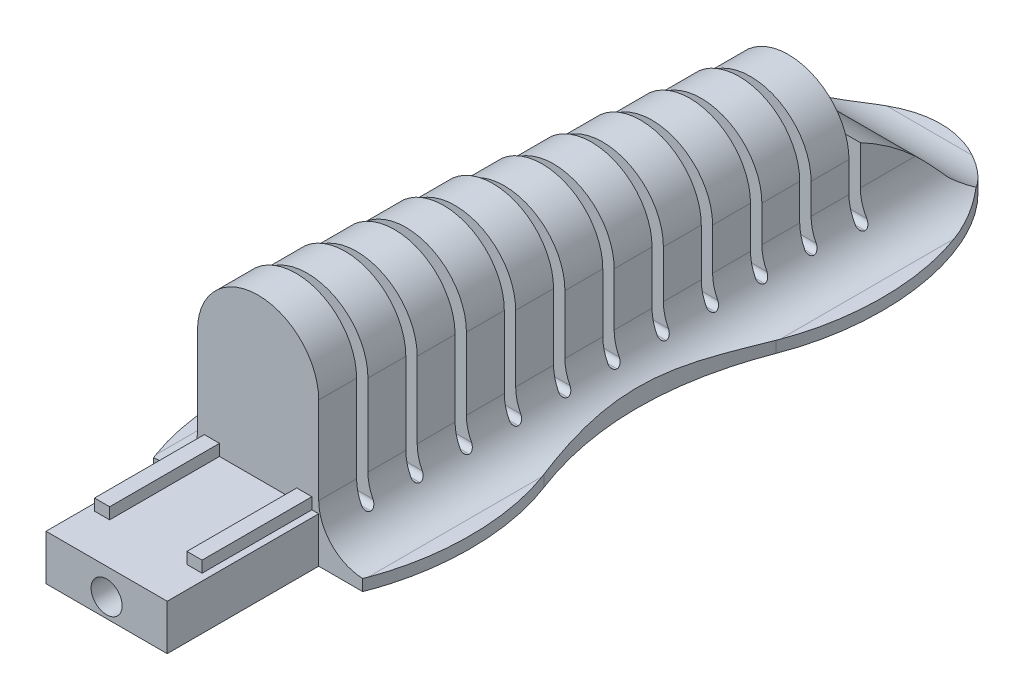
SolidWorks part; units mm, degrees
ref_plane "Front Plane" through (0, 0, 0) normal (0, 0, 1) x (1, 0, 0)
ref_plane "Top Plane" through (0, 0, 0) normal (0, 1, 0) x (1, 0, 0)
ref_plane "Right Plane" through (0, 0, 0) normal (1, 0, 0) x (0, 0, -1)
sketch "Sketch1" plane through (0, 0, 0) normal (0, 0, 1) x (1, 0, 0)
  line L0 (-1.5, -1.5) -> (-1.5, 16.5)
  line L1 (0, 0) -> (5.6, 0)
  line L2 (0, 0) -> (0, 16.5)
  line L4 (13, 0) -> (13, 16.5)
  line L6 (14.5, -1.5) -> (14.5, 16.5)
  line L7 (7.4, 0) -> (13, 0)
  line L9 (7.4, 0) -> (7.4, -1.25)
  line L10 (7.4, -1.25) -> (5.6, -1.25)
  line L11 (5.6, 0) -> (5.6, -1.25)
  line L14 (0, 0) -> (13, 0) construction
  line L15 (-1.5, -1.5) -> (14.5, -1.5) construction
  line L16 (-1.5, -1.5) -> (-1.5, -2.5)
  line L17 (-1.5, -2.5) -> (14.5, -2.5)
  line L18 (14.5, -1.5) -> (14.5, -2.5)
  arc A0 (13, 16.5) -> (0, 16.5) centre (6.5, 16.5) ccw
  arc A1 (14.5, 16.5) -> (-1.5, 16.5) centre (6.5, 16.5) ccw
  point P7 (6.5, 0)
  point P17 (6.5, -2.5)
  dimension "D2" = 6.5
  dimension "D1" = 16.5
  dimension "D4" = 1.25
  dimension "D5" = 1.8
  dimension "D6" = 1.25
  dimension "D3" = 1.5
ref_plane "Plane1" through (0, 0, -6.5) normal (0, 0, 1) x (1, 0, 0)
ref_plane "Plane2" through (0, 0, -13) normal (0, 0, 1) x (1, 0, 0)
ref_plane "Plane3" through (0, 0, -19.5) normal (0, 0, 1) x (1, 0, 0)
ref_plane "Plane4" through (0, 0, -26) normal (0, 0, 1) x (1, 0, 0)
ref_plane "Plane5" through (0, 0, -32.5) normal (0, 0, 1) x (1, 0, 0)
ref_plane "Plane6" through (0, 0, -39) normal (0, 0, 1) x (1, 0, 0)
ref_plane "Plane7" through (0, 0, -45.5) normal (0, 0, 1) x (1, 0, 0)
ref_plane "Plane8" through (0, 0, -52) normal (0, 0, 1) x (1, 0, 0)
ref_plane "Plane9" through (0, 0, -58.5) normal (0, 0, 1) x (1, 0, 0)
ref_plane "Plane10" through (0, 0, -65) normal (0, 0, 1) x (1, 0, 0)
sketch "Sketch2" plane through (0, 0, -6.5) normal (0, 0, 1) x (1, 0, 0)
  line L0 (-1.5, -1.5003) -> (-1.5, 15.75)
  line L1 (0, 0) -> (5.6, 0)
  line L2 (0, 0) -> (0, 15.75)
  line L3 (13, 0) -> (13, 15.75)
  line L4 (14.5, -1.5003) -> (14.5, 15.75)
  line L5 (7.4, 0) -> (13, 0)
  line L6 (7.4, 0) -> (7.4, -1.25)
  line L7 (7.4, -1.25) -> (5.6, -1.25)
  line L8 (5.6, 0) -> (5.6, -1.25)
  line L9 (-1.5, -1.5003) -> (-1.5, -2.5)
  line L10 (-1.5, -2.5) -> (14.5, -2.5)
  line L11 (14.5, -1.5003) -> (14.5, -2.5)
  line L12 (-1.5, 15.75) -> (0, 15.75) construction
  line L13 (13, 15.75) -> (14.5, 15.75) construction
  arc A0 (13, 15.75) -> (0, 15.75) centre (6.5, 15.75) ccw
  arc A1 (14.5, 15.75) -> (-1.5, 15.75) centre (6.5, 15.75) ccw
  point P6 (8.869, 1.1917)
  dimension "D1" = 6.5
  dimension "D7" = 1.5
  dimension "D2" = 1.25
  dimension "D3" = 1.8
  dimension "D4" = 2.5
  dimension "D5" = 15.75
  dimension "D6" = 1.5
  dimension "D8" = 1.5
  dimension "D9" = 5.6
sketch "Sketch4" plane through (0, 0, -13) normal (0, 0, 1) x (1, 0, 0)
  line L0 (-1.5, -2.5) -> (-1.5, 15)
  line L1 (0, 0) -> (5.6, 0)
  line L2 (0, 0) -> (0, 15)
  line L3 (13, 0) -> (13, 15)
  line L4 (14.5, -1.5003) -> (14.5, 15)
  line L5 (7.4, 0) -> (13, 0)
  line L6 (7.4, 0) -> (7.4, -1.25)
  line L7 (7.4, -1.25) -> (5.6, -1.25)
  line L8 (5.6, 0) -> (5.6, -1.25)
  line L10 (-1.5, -2.5) -> (14.5, -2.5)
  line L11 (14.5, -1.5003) -> (14.5, -2.5)
  line L12 (-1.5, 15) -> (0, 15) construction
  line L13 (13, 15) -> (14.5, 15) construction
  arc A0 (13, 15) -> (0, 15) centre (6.5, 15) ccw
  arc A1 (14.5, 15) -> (-1.5, 15) centre (6.5, 15) ccw
  dimension "D1" = 6.5
  dimension "D2" = 1.25
  dimension "D3" = 1.8
  dimension "D4" = 15
  dimension "D5" = 1.5
  dimension "D6" = 2.5
  dimension "D8" = 1.5
  dimension "D9" = 5.6
sketch "Sketch6" plane through (0, 0, -65) normal (0, 0, 1) x (1, 0, 0)
  line L0 (-1.5, -2.5) -> (-1.5, 9)
  line L1 (0, 0) -> (5.6, 0)
  line L2 (0, 0) -> (0, 9)
  line L3 (13, 0) -> (13, 9)
  line L4 (14.5, -1.5003) -> (14.5, 9)
  line L5 (7.4, 0) -> (13, 0)
  line L6 (7.4, 0) -> (7.4, -1.25)
  line L7 (7.4, -1.25) -> (5.6, -1.25)
  line L8 (5.6, 0) -> (5.6, -1.25)
  line L10 (-1.5, -2.5) -> (14.5, -2.5)
  line L11 (14.5, -1.5003) -> (14.5, -2.5)
  line L12 (-1.5, 9) -> (0, 9) construction
  line L13 (13, 9) -> (14.5, 9) construction
  arc A0 (13, 9) -> (0, 9) centre (6.5, 9) ccw
  arc A1 (14.5, 9) -> (-1.5, 9) centre (6.5, 9) ccw
  point P6 (0.8109, -4.9532)
  dimension "D1" = 6.5
  dimension "D2" = 1.25
  dimension "D3" = 1.8
  dimension "D4" = 9
  dimension "D5" = 1.5
  dimension "D6" = 2.5
  dimension "D8" = 1.5
  dimension "D9" = 5.6
sketch "Sketch7" plane through (0, 0, -58.5) normal (0, 0, 1) x (1, 0, 0)
  line L0 (-1.5, -2.5) -> (-1.5, 9.75)
  line L1 (0, 0) -> (5.6, 0)
  line L2 (0, 0) -> (0, 9.75)
  line L3 (13, 0) -> (13, 9.75)
  line L4 (14.5, -1.5003) -> (14.5, 9.75)
  line L5 (7.4, 0) -> (13, 0)
  line L6 (7.4, 0) -> (7.4, -1.25)
  line L7 (7.4, -1.25) -> (5.6, -1.25)
  line L8 (5.6, 0) -> (5.6, -1.25)
  line L10 (-1.5, -2.5) -> (14.5, -2.5)
  line L11 (14.5, -1.5003) -> (14.5, -2.5)
  line L12 (-1.5, 9.75) -> (0, 9.75) construction
  line L13 (13, 9.75) -> (14.5, 9.75) construction
  arc A0 (13, 9.75) -> (0, 9.75) centre (6.5, 9.75) ccw
  arc A1 (14.5, 9.75) -> (-1.5, 9.75) centre (6.5, 9.75) ccw
  point P6 (24.5465, 0.0392)
  dimension "D1" = 6.5
  dimension "D2" = 1.25
  dimension "D3" = 1.8
  dimension "D4" = 9.75
  dimension "D5" = 1.5
  dimension "D6" = 2.5
  dimension "D8" = 1.5
  dimension "D9" = 5.6
sketch "Sketch8" plane through (0, 0, -52) normal (0, 0, 1) x (1, 0, 0)
  line L0 (-1.5, 0.027) -> (-1.5, 10.5)
  line L1 (0, 0) -> (5.6, 0)
  line L2 (0, 0) -> (0, 10.5)
  line L3 (13, 0) -> (13, 10.5)
  line L4 (14.5, -1.5003) -> (14.5, 10.5)
  line L5 (7.4, 0) -> (13, 0)
  line L6 (7.4, 0) -> (7.4, -1.25)
  line L7 (7.4, -1.25) -> (5.6, -1.25)
  line L8 (5.6, 0) -> (5.6, -1.25)
  line L9 (-1.5, 0.027) -> (-1.5, -2.5)
  line L10 (-1.5, -2.5) -> (14.5, -2.5)
  line L11 (14.5, -1.5003) -> (14.5, -2.5)
  line L12 (-1.5, 10.5) -> (0, 10.5) construction
  line L13 (13, 10.5) -> (14.5, 10.5) construction
  arc A0 (13, 10.5) -> (0, 10.5) centre (6.5, 10.5) ccw
  arc A1 (14.5, 10.5) -> (-1.5, 10.5) centre (6.5, 10.5) ccw
  point P6 (11.3324, 2.719)
  dimension "D1" = 6.5
  dimension "D2" = 1.25
  dimension "D3" = 1.8
  dimension "D4" = 10.5
  dimension "D5" = 1.5
  dimension "D6" = 2.5
  dimension "D8" = 1.5
  dimension "D9" = 5.6
sketch "Sketch10" plane through (0, 0, -45.5) normal (0, 0, 1) x (1, 0, 0)
  line L0 (-1.5, -0.8141) -> (-1.5, 11.25)
  line L1 (0, 0) -> (5.6, 0)
  line L2 (0, 0) -> (0, 11.25)
  line L3 (13, 0) -> (13, 11.25)
  line L4 (14.5, -1.5003) -> (14.5, 11.25)
  line L5 (7.4, 0) -> (13, 0)
  line L6 (7.4, 0) -> (7.4, -1.25)
  line L7 (7.4, -1.25) -> (5.6, -1.25)
  line L8 (5.6, 0) -> (5.6, -1.25)
  line L9 (-1.5, -0.8141) -> (-1.5, -2.5)
  line L10 (-1.5, -2.5) -> (14.5, -2.5)
  line L11 (14.5, -1.5003) -> (14.5, -2.5)
  line L12 (-1.5, 11.25) -> (0, 11.25) construction
  line L13 (13, 11.25) -> (14.5, 11.25) construction
  arc A0 (13, 11.25) -> (0, 11.25) centre (6.5, 11.25) ccw
  arc A1 (14.5, 11.25) -> (-1.5, 11.25) centre (6.5, 11.25) ccw
  point P6 (9.5449, 1.8779)
  dimension "D1" = 6.5
  dimension "D2" = 1.25
  dimension "D3" = 1.8
  dimension "D4" = 11.25
  dimension "D5" = 1.5
  dimension "D6" = 2.5
  dimension "D8" = 1.5
  dimension "D9" = 5.6
sketch "Sketch11" plane through (0, 0, -39) normal (0, 0, 1) x (1, 0, 0)
  line L0 (-1.5, -1.3963) -> (-1.5, 12)
  line L1 (0, 0) -> (5.6, 0)
  line L2 (0, 0) -> (0, 12)
  line L3 (13, 0) -> (13, 12)
  line L4 (14.5, -1.5003) -> (14.5, 12)
  line L5 (7.4, 0) -> (13, 0)
  line L6 (7.4, 0) -> (7.4, -1.25)
  line L7 (7.4, -1.25) -> (5.6, -1.25)
  line L8 (5.6, 0) -> (5.6, -1.25)
  line L9 (-1.5, -1.3963) -> (-1.5, -2.5)
  line L10 (-1.5, -2.5) -> (14.5, -2.5)
  line L11 (14.5, -1.5003) -> (14.5, -2.5)
  line L12 (-1.5, 12) -> (0, 12) construction
  line L13 (13, 12) -> (14.5, 12) construction
  arc A0 (13, 12) -> (0, 12) centre (6.5, 12) ccw
  arc A1 (14.5, 12) -> (-1.5, 12) centre (6.5, 12) ccw
  point P6 (10.4063, 1.2956)
  dimension "D1" = 6.5
  dimension "D2" = 1.25
  dimension "D3" = 1.8
  dimension "D4" = 12
  dimension "D5" = 1.5
  dimension "D6" = 2.5
  dimension "D8" = 1.5
  dimension "D9" = 5.6
sketch "Sketch12" plane through (0, 0, -32.5) normal (0, 0, 1) x (1, 0, 0)
  line L0 (-1.5, -0.8222) -> (-1.5, 12.75)
  line L1 (0, 0) -> (5.6, 0)
  line L2 (0, 0) -> (0, 12.75)
  line L3 (13, 0) -> (13, 12.75)
  line L4 (14.5, -1.5003) -> (14.5, 12.75)
  line L5 (7.4, 0) -> (13, 0)
  line L6 (7.4, 0) -> (7.4, -1.25)
  line L7 (7.4, -1.25) -> (5.6, -1.25)
  line L8 (5.6, 0) -> (5.6, -1.25)
  line L9 (-1.5, -0.8222) -> (-1.5, -2.5)
  line L10 (-1.5, -2.5) -> (14.5, -2.5)
  line L11 (14.5, -1.5003) -> (14.5, -2.5)
  line L12 (-1.5, 12.75) -> (0, 12.75) construction
  line L13 (13, 12.75) -> (14.5, 12.75) construction
  arc A0 (13, 12.75) -> (0, 12.75) centre (6.5, 12.75) ccw
  arc A1 (14.5, 12.75) -> (-1.5, 12.75) centre (6.5, 12.75) ccw
  point P6 (11.2276, 1.8697)
  dimension "D1" = 6.5
  dimension "D2" = 1.25
  dimension "D3" = 1.8
  dimension "D4" = 12.75
  dimension "D5" = 1.5
  dimension "D6" = 2.5
  dimension "D8" = 1.5
  dimension "D9" = 5.6
sketch "Sketch13" plane through (0, 0, -26) normal (0, 0, 1) x (1, 0, 0)
  line L0 (-1.5, -0.309) -> (-1.5, 13.75)
  line L1 (0, 0) -> (5.6, 0)
  line L2 (0, 0) -> (0, 13.75)
  line L3 (13, 0) -> (13, 13.75)
  line L4 (14.5, -1.5003) -> (14.5, 13.75)
  line L5 (7.4, 0) -> (13, 0)
  line L6 (7.4, 0) -> (7.4, -1.25)
  line L7 (7.4, -1.25) -> (5.6, -1.25)
  line L8 (5.6, 0) -> (5.6, -1.25)
  line L9 (-1.5, -0.309) -> (-1.5, -2.5)
  line L10 (-1.5, -2.5) -> (14.5, -2.5)
  line L11 (14.5, -1.5003) -> (14.5, -2.5)
  line L12 (-1.5, 13.75) -> (0, 13.75) construction
  line L13 (13, 13.75) -> (14.5, 13.75) construction
  arc A0 (13, 13.75) -> (0, 13.75) centre (6.5, 13.75) ccw
  arc A1 (14.5, 13.75) -> (-1.5, 13.75) centre (6.5, 13.75) ccw
  point P6 (9.7613, 2.3829)
  dimension "D1" = 6.5
  dimension "D2" = 1.25
  dimension "D3" = 1.8
  dimension "D4" = 13.75
  dimension "D5" = 1.5
  dimension "D6" = 2.5
  dimension "D8" = 1.5
  dimension "D9" = 5.6
sketch "Sketch14" plane through (0, 0, -19.5) normal (0, 0, 1) x (1, 0, 0)
  line L0 (-1.5, -2.5) -> (-1.5, 14.5)
  line L1 (0, 0) -> (5.6, 0)
  line L2 (0, 0) -> (0, 14.5)
  line L3 (13, 0) -> (13, 14.5)
  line L4 (14.5, -1.5003) -> (14.5, 14.5)
  line L5 (7.4, 0) -> (13, 0)
  line L6 (7.4, 0) -> (7.4, -1.25)
  line L7 (7.4, -1.25) -> (5.6, -1.25)
  line L8 (5.6, 0) -> (5.6, -1.25)
  line L10 (-1.5, -2.5) -> (14.5, -2.5)
  line L11 (14.5, -1.5003) -> (14.5, -2.5)
  line L12 (-1.5, 14.5) -> (0, 14.5) construction
  line L13 (13, 14.5) -> (14.5, 14.5) construction
  arc A0 (13, 14.5) -> (0, 14.5) centre (6.5, 14.5) ccw
  arc A1 (14.5, 14.5) -> (-1.5, 14.5) centre (6.5, 14.5) ccw
  point P6 (16.0051, -5.4208)
  dimension "D1" = 6.5
  dimension "D2" = 1.25
  dimension "D3" = 1.8
  dimension "D4" = 14.5
  dimension "D5" = 1.5
  dimension "D6" = 2.5
  dimension "D8" = 1.5
  dimension "D9" = 5.6
extrude "Boss-Extrude3" add sketch "Sketch1" against normal blind 3.5 and the other way blind 1.5 contours L17 L18 L6 A1 L0 L16
extrude "Boss-Extrude4" add sketch "Sketch2" along normal blind 1.5 and the other way blind 3.5 separate body contours L10 L11 L4 A1 L0 L9
extrude "Boss-Extrude5" add sketch "Sketch4" along normal blind 1.5 and the other way blind 3.5 separate body contours L10 L11 L4 A1 L0
extrude "Boss-Extrude6" add sketch "Sketch14" along normal blind 1.5 and the other way blind 3.5 separate body contours L10 L11 L4 A1 L0
extrude "Boss-Extrude7" add sketch "Sketch13" along normal blind 1.5 and the other way blind 3.5 separate body contours L10 L11 L4 A1 L0 L9
extrude "Boss-Extrude8" add sketch "Sketch12" along normal blind 1.5 and the other way blind 3.5 separate body contours L10 L11 L4 A1 L0 L9
extrude "Boss-Extrude9" add sketch "Sketch11" along normal blind 1.5 and the other way blind 3.5 separate body contours L10 L11 L4 A1 L0 L9
extrude "Boss-Extrude10" add sketch "Sketch10" along normal blind 1.5 and the other way blind 3.5 separate body contours L10 L11 L4 A1 L0 L9
extrude "Boss-Extrude11" add sketch "Sketch8" along normal blind 1.5 and the other way blind 3.5 separate body contours L10 L11 L4 A1 L0 L9
extrude "Boss-Extrude12" add sketch "Sketch7" along normal blind 1.5 and the other way blind 3.5 separate body contours L10 L11 L4 A1 L0
extrude "Boss-Extrude13" add sketch "Sketch6" along normal blind 1.5 and the other way blind 3.5 separate body contours L10 L11 L4 A1 L0
sketch "Sketch15" plane through (0, 0, 1.5) normal (0, 0, 1) x (1, 0, 0)
  line L0 (14.5, 16.5) -> (14.5, -2.5) construction
  line L1 (-1.5, -2.5) -> (14.5, -2.5)
  line L2 (-1.5, -2.5) -> (-1.5, 1.5)
  line L3 (-1.5, 1.5) -> (14.5, 1.5)
  line L4 (14.5, -2.5) -> (14.5, 1.5)
  line L5 (0, 0) -> (5.6, 0) construction
  line L7 (5.6, -1.25) -> (7.4, -1.25)
  line L8 (5.6, -1.25) -> (5.6, 0)
  line L9 (5.6, 0) -> (7.4, 0)
  line L10 (7.4, -1.25) -> (7.4, 0)
  dimension "D1" = 1.5
extrude "Boss-Extrude14" add sketch "Sketch15" against normal up to surface (70 mm away) contours L1 L4 L3 L2 up to face at (6.5, 5.25, -68.5)
extrude "Cut-Extrude1" cut sketch "Sketch1<4>" against normal blind 2 contours L1 L11 L10 L9 L7 L4 A0 L2
sketch "Sketch1<4>" plane through (0, 0, 0) normal (0, 0, 1) x (1, 0, 0) same geometry as "Sketch1"
extrude "Cut-Extrude2" cut sketch "Sketch2<3>" against normal blind 2 contours L1 L8 L7 L6 L5 L3 A0 L2
sketch "Sketch2<3>" plane through (0, 0, -6.5) normal (0, 0, 1) x (1, 0, 0) same geometry as "Sketch2"
extrude "Cut-Extrude3" cut sketch "Sketch4<3>" against normal blind 2 contours L1 L8 L7 L6 L5 L3 A0 L2
sketch "Sketch4<3>" plane through (0, 0, -13) normal (0, 0, 1) x (1, 0, 0) same geometry as "Sketch4"
extrude "Cut-Extrude4" cut sketch "Sketch14<3>" against normal blind 2 contours L1 L8 L7 L6 L5 L3 A0 L2
sketch "Sketch14<3>" plane through (0, 0, -19.5) normal (0, 0, 1) x (1, 0, 0) same geometry as "Sketch14"
extrude "Cut-Extrude5" cut sketch "Sketch13<3>" against normal blind 2 contours L1 L8 L7 L6 L5 L3 A0 L2
sketch "Sketch13<3>" plane through (0, 0, -26) normal (0, 0, 1) x (1, 0, 0) same geometry as "Sketch13"
extrude "Cut-Extrude6" cut sketch "Sketch12<3>" against normal blind 2 contours L1 L8 L7 L6 L5 L3 A0 L2
sketch "Sketch12<3>" plane through (0, 0, -32.5) normal (0, 0, 1) x (1, 0, 0) same geometry as "Sketch12"
extrude "Cut-Extrude7" cut sketch "Sketch11<3>" against normal blind 2 contours L1 L8 L7 L6 L5 L3 A0 L2
sketch "Sketch11<3>" plane through (0, 0, -39) normal (0, 0, 1) x (1, 0, 0) same geometry as "Sketch11"
extrude "Cut-Extrude8" cut sketch "Sketch10<3>" against normal blind 2 contours L1 L8 L7 L6 L5 L3 A0 L2
sketch "Sketch10<3>" plane through (0, 0, -45.5) normal (0, 0, 1) x (1, 0, 0) same geometry as "Sketch10"
extrude "Cut-Extrude9" cut sketch "Sketch8<3>" against normal blind 2 contours L1 L8 L7 L6 L5 L3 A0 L2
sketch "Sketch8<3>" plane through (0, 0, -52) normal (0, 0, 1) x (1, 0, 0) same geometry as "Sketch8"
extrude "Cut-Extrude10" cut sketch "Sketch7<3>" against normal blind 2 contours L1 L8 L7 L6 L5 L3 A0 L2
sketch "Sketch7<3>" plane through (0, 0, -58.5) normal (0, 0, 1) x (1, 0, 0) same geometry as "Sketch7"
extrude "Cut-Extrude11" cut sketch "Sketch6<3>" against normal blind 2 contours L1 L8 L7 L6 L5 L3 A0 L2
sketch "Sketch6<3>" plane through (0, 0, -65) normal (0, 0, 1) x (1, 0, 0) same geometry as "Sketch6"
extrude "Cut-Extrude12" cut sketch "Sketch15<3>" against normal offset from surface (68.5 mm away) 1.5 contours L7 L10 L9 L8 up to face at (6.5, 5.25, -68.5)
sketch "Sketch15<3>" plane through (0, 0, 1.5) normal (0, 0, 1) x (1, 0, 0) same geometry as "Sketch15"
sketch "Sketch16" plane through (0, 0, 1.5) normal (0, 0, 1) x (1, 0, 0)
  line L0 (5.6, 0) -> (7.4, 0) construction
  line L1 (14.5, 16.5) -> (14.5, -2.5) construction
  line L2 (-1.5, -2.5) -> (14.5, -2.5)
  line L3 (-1.5, -2.5) -> (-1.5, 3.5)
  line L4 (-1.5, 3.5) -> (14.5, 3.5)
  line L5 (14.5, -2.5) -> (14.5, 3.5)
  circle A0 centre (6.5, 0) radius 2.05
  dimension "D1" = 4.1
  dimension "D2" = 6
extrude "Boss-Extrude15" add sketch "Sketch16" along normal blind 20
sketch "Sketch17" plane through (0, 3.5, 0) normal (0, 1, 0) x (1, 0, 0)
  line L0 (14.5, -1.5) -> (-1.5, -1.5) construction
  line L1 (-0.6, -1.5) -> (1.4, -1.5)
  line L2 (-0.6, -1.5) -> (-0.6, -16)
  line L3 (-0.6, -16) -> (1.4, -16)
  line L4 (1.4, -1.5) -> (1.4, -16)
  line L5 (-1.5, -1.5) -> (14.5, -1.5) construction
  line L6 (11.6, -1.5) -> (13.6, -1.5)
  line L7 (11.6, -1.5) -> (11.6, -16)
  line L8 (11.6, -16) -> (13.6, -16)
  line L9 (13.6, -1.5) -> (13.6, -16)
  point P12 (6.5, -1.5)
  line M1 (14.5, -1.5) -> (-1.5, -1.5)
  dimension "D1" = 14.5
  dimension "D2" = 14.5
  dimension "D3" = 2
  dimension "D4" = 2
  dimension "D5" = 10.2
  dimension "D6" = 5.1
extrude "Boss-Extrude16" add sketch "Sketch17" along normal blind 1.5 contours L9 L7 L8 M1 | L3 L4 L1 L2 region at (12.6, 3.5, 8.75)
sketch "Sketch21" plane through (0, -2.5, 0) normal (0, -1, 0) x (1, 0, 0)
  line L0 (-1.5, 1.5) -> (20.3074, 1.5)
  line L1 (20.3074, 1.5) -> (-7.3074, 1.5)
  line L2 (6.5, -64.8964) -> (6.5, -41.1464) construction
  line L3 (14.5, -68.5) -> (-1.5, -68.5) construction
  line L4 (6.5, -68.5) -> (6.5, 1.5) construction
  line L5 (6.5, -41.1464) -> (6.5, -53.0214) construction
  line L6 (6.5, -53.0214) -> (-7.3564, -53.0214) construction
  line L7 (-7.3564, -53.0214) -> (20.3564, -53.0214) construction
  line L8 (6.5, -10.5) -> (6.5, -34.25) construction
  line L9 (6.5, -34.25) -> (6.5, -10.5) construction
  line L10 (6.5, -10.5) -> (6.5, -22.375) construction
  line L11 (6.5, -22.375) -> (20.3564, -22.375) construction
  line L12 (20.3564, -22.375) -> (-7.3564, -22.375) construction
  line L13 (-1.5, -37.5) -> (20.3564, -37.5) construction
  line L14 (20.3564, -37.5) -> (-7.3564, -37.5) construction
  line L15 (-7.3564, -37.5) -> (-1.5, -37.5) construction
  line L16 (-1.5, -37.5) -> (-4.4282, -37.5) construction
  line L17 (-4.4282, -37.5) -> (20.3564, -37.5) construction
  line L18 (20.3564, -37.5) -> (14.5, -37.5) construction
  line L19 (14.5, -37.5) -> (17.4282, -37.5) construction
  line L21 (-22.0147, 1.5) -> (35.3246, 1.5)
  line L22 (-22.0147, 1.5) -> (-22.0147, -102.7678)
  line L23 (-22.0147, -102.7678) -> (35.3246, -102.7678)
  line L24 (35.3246, 1.5) -> (35.3246, -102.7678)
  ellipse E0 centre (6.5, -64.8964) end of major axis (6.5, -88.6464) minor radius 16 (-7.3564, -53.0214) -> (20.3564, -53.0214) ccw
  ellipse E1 centre (6.5, -10.5) end of major axis (6.5, -34.25) minor radius 16 (-7.3074, 1.5) -> (-7.3564, -22.375) ccw
  ellipse E2 centre (6.5, -10.5) end of major axis (6.5, -34.25) minor radius 16 (20.3564, -22.375) -> (20.3074, 1.5) ccw
  spline S0 degree 2 poles (20.3564, -22.375) (14.4991, -37.6842) (20.3564, -53.0214) knots 0 0 0 1 1 1
  spline S1 degree 2 poles (-7.3564, -22.375) (-1.4991, -37.6842) (-7.3564, -53.0214) knots 0 0 0 1 1 1
  dimension "D1" = 23.75
  dimension "D2" = 16
  dimension "D3" = 23.75
  dimension "D4" = 16
  dimension "D5" = 12
sketch "Sketch22" plane through (14.5, 0, 0) normal (1, 0, 0) x (0, 0, -1)
  line L0 (70, 1.1761) -> (70, 10.1761)
  line L1 (68.5, -2.5) -> (80.5, -2.5)
  line L2 (68.5, -2.5) -> (68.5, 1.1761)
  line L3 (68.5, 1.1761) -> (70, 1.1761)
  line L4 (80.5, -2.5) -> (80.5, 1.5)
  line L5 (68.5, 9) -> (68.5, -2.5) construction
  arc A1 (80.5, 1.5) -> (70, 10.1761) centre (54.272, -19.5498) ccw
  dimension "D2" = 12
  dimension "D1" = 4
  dimension "D3" = 1.5
  dimension "D4" = 9
extrude "Boss-Extrude18" add sketch "Sketch22" against normal up to surface (16 mm away) contours L1 L4 A1 L0 L3 L2 up to face at (-1.5, 6.8152, -31.1087)
sketch "Sketch23" plane through (0, 0, 1.5) normal (0, 0, 1) x (1, 0, 0)
  line L0 (-9.5, -2.5) -> (22.5, -2.5) construction
  line L2 (-9.5, -2.5) -> (-9.5, -1)
  line L3 (-9.5, -1) -> (-7.5, -1)
  line L4 (22.5, -2.5) -> (22.5, -1)
  line L5 (-1.5, 3.5) -> (-1.5, -2.5) construction
  line L6 (-1.5, 5) -> (-1.5, -1)
  line L7 (14.5, -2.5) -> (14.5, 3.5) construction
  line L9 (14.5, 5) -> (14.5, -1)
  line L10 (20.5, -1) -> (22.5, -1)
  line L11 (-9.5, -2.5) -> (-1.5, -2.5)
  line L12 (-1.5, -2.5) -> (-1.5, -1)
  line L13 (14.5, -1) -> (14.5, -2.5)
  line L14 (14.5, -2.5) -> (22.5, -2.5)
  arc A0 (-7.5, -1) -> (-1.5, 5) centre (-7.5, 5) ccw
  arc A1 (14.5, 5) -> (20.5, -1) centre (20.5, 5) ccw
  dimension "D2" = 12
  dimension "D3" = 12
  dimension "D1" = 1.5
extrude "Boss-Extrude19" add sketch "Sketch23" against normal up to surface (82 mm away) separate body contours A0 L6 L12 L11 L2 L3 | A1 L10 L4 L14 L13 L9 up to face at (6.5, -0.5, -80.5)
sketch "Sketch24" plane through (14.5, 0, 0) normal (1, 0, 0) x (0, 0, -1)
  line L0 (69.1958, 10.5879) -> (88.0362, 13.8618)
  line L1 (88.0362, 13.8618) -> (82.8289, -1.7873)
  line L2 (80.5, 1.5) -> (80.5, -2.5)
  line L3 (80.5, -2.5) -> (83.26, -2.5)
  line L4 (53.0214, -2.5) -> (88.6464, -2.5) construction
  arc A0 (83.26, -2.5) -> (69.1958, 10.5879) centre (54.272, -19.5498) ccw
  arc M3 (80.5, 1.5) -> (70, 10.1761) centre (54.272, -19.5498) ccw
extrude "Cut-Extrude13" cut sketch "Sketch24" against normal through all both and the other way through all contours A0 L1 L0 M3 region at (14.5, 7.9108, -80.4913)
extrude "Boss-Extrude20" add sketch "Sketch21" against normal blind 1.5 contours L1 E1 S1 E0 S0 E2
extrude "Cut-Extrude14" cut sketch "Sketch21<4>" against normal through all both and the other way through all contours S1 E1 L21 L22 L23 L24 E2 S0 E0 region at (27.816, -2.5, 0.3101)
sketch "Sketch21<4>" plane through (0, -2.5, 0) normal (0, -1, 0) x (1, 0, 0) same geometry as "Sketch21"
fillet "Fillet1" radius 10 1 edges at (6.5, -1, -80.5)
sketch "Sketch27" plane through (14.5, 0, 0) normal (-1, 0, 0) x (0, 0, 1)
  line L0 (-5, 1.5) -> (-3.5, 1.5) construction
  line L1 (-5, 5) -> (-3.5, 5)
  line L2 (-5, 5) -> (-5, 1.5)
  line L3 (-5, 1.5) -> (-3.5, 1.5)
  line L4 (-3.5, 5) -> (-3.5, 1.5)
  line L5 (-18, 1.5) -> (-18, 5) construction
  line L6 (-11.5, 5) -> (-10, 5)
  line L7 (-11.5, 5) -> (-11.5, 1.5)
  line L8 (-11.5, 1.5) -> (-10, 1.5)
  line L9 (-10, 5) -> (-10, 1.5)
  line L10 (-18, 5) -> (-16.5, 5)
  line L11 (-18, 5) -> (-18, 1.5)
  line L12 (-18, 1.5) -> (-16.5, 1.5)
  line L13 (-16.5, 5) -> (-16.5, 1.5)
  line L14 (-37.5, 5) -> (-37.5, 1.5) construction
  line L15 (-23, 5) -> (-24.5, 5)
  line L16 (-23, 5) -> (-23, 1.5)
  line L17 (-23, 1.5) -> (-24.5, 1.5)
  line L18 (-24.5, 5) -> (-24.5, 1.5)
  line L19 (-29.5, 5) -> (-31, 5)
  line L20 (-29.5, 5) -> (-29.5, 1.5)
  line L21 (-29.5, 1.5) -> (-31, 1.5)
  line L22 (-31, 5) -> (-31, 1.5)
  line L23 (-37.5, 5) -> (-36, 5)
  line L24 (-37.5, 5) -> (-37.5, 1.5)
  line L25 (-37.5, 1.5) -> (-36, 1.5)
  line L26 (-36, 5) -> (-36, 1.5)
  line L27 (-57, 1.5) -> (-55.5, 1.5) construction
  line L28 (-42.5, 5) -> (-44, 5)
  line L29 (-42.5, 5) -> (-42.5, 1.5)
  line L30 (-42.5, 1.5) -> (-44, 1.5)
  line L31 (-44, 5) -> (-44, 1.5)
  line L32 (-49, 5) -> (-50.5, 5)
  line L33 (-49, 5) -> (-49, 1.5)
  line L34 (-49, 1.5) -> (-50.5, 1.5)
  line L35 (-50.5, 5) -> (-50.5, 1.5)
  line L36 (-55.5, 5) -> (-57, 5)
  line L37 (-55.5, 5) -> (-55.5, 1.5)
  line L38 (-55.5, 1.5) -> (-57, 1.5)
  line L39 (-57, 5) -> (-57, 1.5)
  line L41 (-62, 5) -> (-63.5, 5)
  line L42 (-62, 5) -> (-62, 1.5)
  line L43 (-62, 1.5) -> (-63.5, 1.5)
  line L44 (-63.5, 5) -> (-63.5, 1.5)
  line L45 (-68.5, 5) -> (-70, 5)
  line L46 (-68.5, 5) -> (-68.5, 1.1761)
  line L47 (-68.5, 1.1761) -> (-70, 1.1761)
  line L48 (-70, 5) -> (-70, 1.1761)
extrude "Cut-Extrude15" cut sketch "Sketch27" against normal through all both and the other way through all
fillet "Fillet2" radius 0.75 22 edges at (6.5, 1.1761, -68.5) (6.5, 1.1761, -70) (6.5, 1.5, -62) (6.5, 1.5, -63.5) (6.5, 1.5, -55.5) (6.5, 1.5, -57) (6.5, 1.5, -49) (6.5, 1.5, -50.5) (6.5, 1.5, -42.5) (6.5, 1.5, -44) (6.5, 1.5, -36) (6.5, 1.5, -37.5) (6.5, 1.5, -29.5) (6.5, 1.5, -31) (6.5, 1.5, -23) (6.5, 1.5, -24.5) (6.5, 1.5, -18) (6.5, 1.5, -16.5) (6.5, 1.5, -3.5) (6.5, 1.5, -5) (6.5, 1.5, -10) (6.5, 1.5, -11.5)
sketch "Sketch29" plane through (0, 0, 0) normal (1, 0, 0) x (0, 0, -1)
  line L3 (73.5, 0) -> (73.5, 6.1921)
  line L5 (71.5, 0) -> (71.5, 7.5713)
  line L6 (70, 5) -> (70, 1.9261) construction
  line L8 (71.5, 0) -> (73.5, 0)
  arc A2 (76.2318, 3.905) -> (69.2985, 8.8503) centre (54.272, -19.5498) ccw
  arc A3 (73.5, 6.1921) -> (71.5, 7.5713) centre (54.272, -19.5498) ccw
  dimension "D2" = 1.5
  dimension "D3" = 2
  dimension "D1" = 1.5
extrude "Cut-Extrude18" cut sketch "Sketch29" along normal up to surface (13 mm away) contours L5 A3 L3 L8 up to face at (13, 4.5, -66)
sketch "Sketch30" plane through (0, 0, -67) normal (0, 0, 1) x (1, 0, 0)
  line L1 (7.4, -1) -> (5.6, -1)
  line L2 (7.4, -1) -> (7.4, 0)
  line L3 (7.4, 0) -> (5.6, 0)
  line L4 (5.6, -1) -> (5.6, 0)
extrude "Cut-Extrude19" cut sketch "Sketch30" against normal up to surface (6.5 mm away) up to face at (6.5, 3.096, -73.5)
equation "\"h\"=16.5"
equation "\"D1@Sketch1\"=\"h\""
